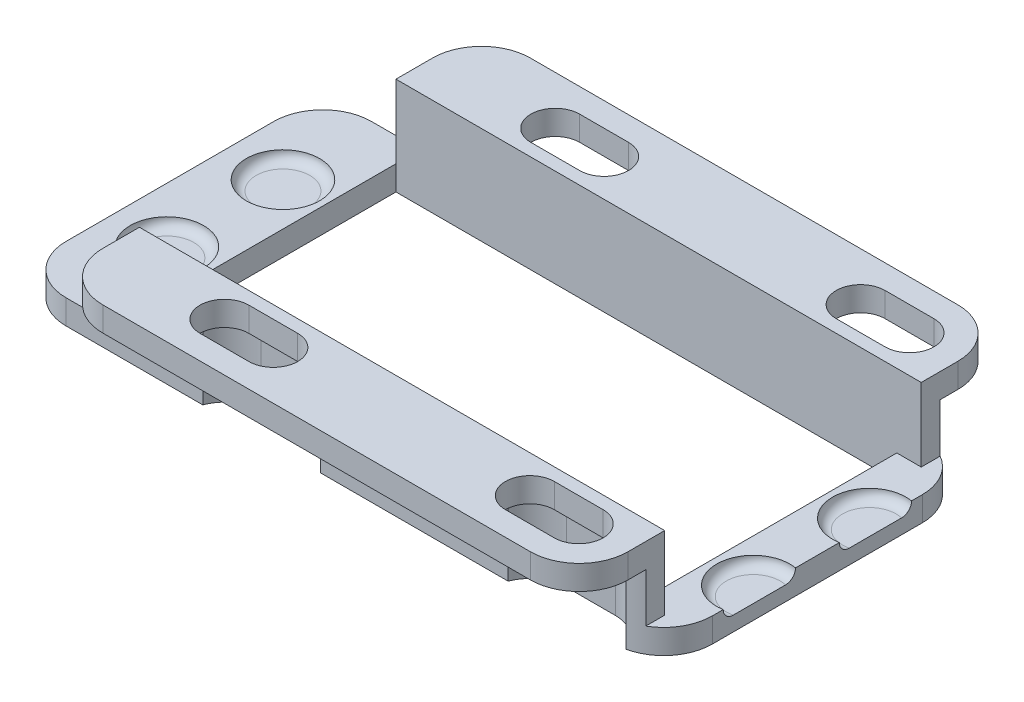
SolidWorks part; units mm, degrees
material "自定义塑料"
ref_plane "前视基准面" through (0, 0, 0) normal (0, 0, 1) x (1, 0, 0)
ref_plane "上视基准面" through (0, 0, 0) normal (0, 1, 0) x (1, 0, 0)
ref_plane "右视基准面" through (0, 0, 0) normal (1, 0, 0) x (0, 0, -1)
sketch "草图4" plane through (0, 0, 0) normal (0, 1, 0) x (1, 0, 0)
  line L0 (20.5, 10.5) -> (24.5, 10.5)
  line L1 (-20.5, 10.5) -> (20.5, 10.5)
  line L2 (-20.5, 10.5) -> (-20.5, -10.5)
  line L3 (-20.5, -10.5) -> (20.5, -10.5)
  line L4 (20.5, 10.5) -> (20.5, -10.5)
  line L5 (-20.5, 10.5) -> (20.5, -10.5) construction
  line L6 (-20.5, -10.5) -> (20.5, 10.5) construction
  line L7 (24.5, 10.5) -> (24.5, 12.5)
  line L9 (-24.5, -12.5) -> (24.5, -12.5)
  line L11 (-24.5, 12.5) -> (24.5, 12.5)
  line L12 (24.5, -12.5) -> (24.5, 12.5)
  line L13 (-24.5, -12.5) -> (24.5, 12.5) construction
  line L14 (-24.5, 12.5) -> (24.5, -12.5) construction
  line L15 (-24.5, 12.5) -> (-28.5, 12.5)
  line L17 (-24.5, -12.5) -> (-28.5, -12.5)
  line L18 (-28.5, 12.5) -> (-28.5, -12.5)
  point P0 (0, 0)
  point P5 (0, 0)
extrude "凸台-拉伸2" add sketch "草图4" along normal blind 2 contours L15 L18 L17 L9 L12 L4 L3 L2 L1 L7 L11 region at (23.914, 0, 1)
sketch "草图5" plane through (0, 2, 0) normal (0, 1, 0) x (1, 0, 0)
  line L1 (-24, 4.75) -> (24, 4.75)
  line L2 (-24, 4.75) -> (-24, -4.75)
  line L3 (-24, -4.75) -> (24, -4.75)
  line L4 (24, 4.75) -> (24, -4.75)
  line L5 (-24, 4.75) -> (24, -4.75) construction
  line L6 (-24, -4.75) -> (24, 4.75) construction
  circle A0 centre (-24, 4.75) radius 3
  circle A1 centre (-24, -4.75) radius 3
  circle A2 centre (24, 4.75) radius 3
  circle A3 centre (24, -4.75) radius 3
  point P0 (0, 0)
  line M3 (24.5, -12.5) -> (24.5, 12.5)
  dimension "D1" = 48
  dimension "D2" = 9.5
extrude "切除-拉伸2" cut sketch "草图5" against normal blind 0.8 contours L1 A0 L2 | L2 A0 L1 | L2 A1 L3 | L3 A1 L2 | L1 A2 L4 | L4 A2 L1 M3 | A3 L4 L3 M3 | L4 A3 L3 region at (-24.4244, 2, -5.1744) region at (-22.7268, 2, -3.4768) region at (23.179, 2, -5.6451) region at (22.7268, 2, -3.4768) region at (-22.7268, 2, 3.4768) region at (-24.4244, 2, 5.1744) region at (23.179, 2, 5.6451) region at (22.7268, 2, 3.4768)
fillet "圆角1" radius 0.8 4 edges at (21, 1.2, 4.75) (21, 1.2, -4.75) (-24, 1.2, 7.75) (-24, 1.2, -1.75)
sketch "草图6" plane through (0, 2, 0) normal (0, 1, 0) x (1, 0, 0)
  line L0 (24.5, 12.5) -> (-28.5, 12.5) construction
  line L1 (-20.5, 10.5) -> (22.5, 10.5)
  line L2 (-20.5, 10.5) -> (-20.5, 12.5)
  line L3 (-20.5, 12.5) -> (22.5, 12.5)
  line L4 (22.5, 10.5) -> (22.5, 12.5)
  line L5 (24.5, -12.5) -> (-28.5, -12.5) construction
  line L6 (-20.5, -10.5) -> (22.5, -10.5)
  line L7 (-20.5, -10.5) -> (-20.5, -12.5)
  line L8 (-20.5, -12.5) -> (22.5, -12.5)
  line L9 (22.5, -10.5) -> (22.5, -12.5)
extrude "凸台-拉伸3" add sketch "草图6" along normal blind 4
sketch "草图7" plane through (0, 6, 0) normal (0, 1, 0) x (1, 0, 0)
  line L1 (-20.5, 10.5) -> (22.5, 10.5)
  line L2 (-20.5, 10.5) -> (-20.5, 17.5)
  line L3 (-20.5, 17.5) -> (22.5, 17.5)
  line L4 (22.5, 10.5) -> (22.5, 17.5)
  line L5 (-20.5, -10.5) -> (22.5, -10.5)
  line L6 (-20.5, -10.5) -> (-20.5, -17.5)
  line L7 (-20.5, -17.5) -> (22.5, -17.5)
  line L8 (22.5, -10.5) -> (22.5, -17.5)
  dimension "D1" = 7
  dimension "D2" = 7
extrude "凸台-拉伸4" add sketch "草图7" along normal blind 2
sketch "草图8" plane through (0, 0, 0) normal (0, -1, 0) x (1, 0, 0)
  line L0 (-10.5, -15.54) -> (-6.5, -15.54)
  line L1 (-4.5, -13.54) -> (16.5, -13.54)
  line L2 (-8.5, -11.54) -> (-8.5, 13.54)
  line L3 (-8.5, 13.54) -> (16.5, 13.54)
  line L4 (16.5, -13.54) -> (16.5, 13.54)
  line L5 (-8.5, -13.54) -> (16.5, 13.54) construction
  line L6 (-8.5, 13.54) -> (16.5, -13.54) construction
  line L7 (-10.5, -11.54) -> (-6.5, -11.54)
  line L8 (14.5, -15.54) -> (18.5, -15.54)
  line L9 (14.5, -11.54) -> (18.5, -11.54)
  line L10 (14.5, 11.54) -> (18.5, 11.54)
  line L11 (14.5, 15.54) -> (18.5, 15.54)
  line L12 (-10.5, 11.54) -> (-6.5, 11.54)
  line L13 (-10.5, 15.54) -> (-6.5, 15.54)
  line L14 (-10.5, -15.54) -> (14.5, -15.54) construction
  arc A1 (-10.5, -11.54) -> (-10.5, -15.54) centre (-10.5, -13.54) ccw
  arc A2 (-6.5, -15.54) -> (-6.6595, -11.5464) centre (-6.5, -13.54) ccw
  arc A3 (14.5, -11.54) -> (14.5, -15.54) centre (14.5, -13.54) ccw
  arc A4 (18.5, -15.54) -> (18.3405, -11.5464) centre (18.5, -13.54) ccw
  arc A5 (14.5, 15.54) -> (14.5, 11.54) centre (14.5, 13.54) ccw
  arc A6 (18.5, 11.54) -> (18.3405, 15.5336) centre (18.5, 13.54) ccw
  arc A7 (-10.5, 15.54) -> (-10.5, 11.54) centre (-10.5, 13.54) ccw
  arc A8 (-6.5, 11.54) -> (-6.6595, 15.5336) centre (-6.5, 13.54) ccw
  point P0 (0, 0)
  point P1 (4, 0)
  point P3 (4, 0)
  point P12 (0, 0)
  line M29 (24.5, 12.5) -> (-28.5, 12.5)
  line M31 (-28.5, -12.5) -> (24.5, -12.5)
  dimension "D2" = 2
  dimension "D1" = 4
  dimension "D3" = 2
  dimension "D4" = 25
extrude "切除-拉伸3" cut sketch "草图8" against normal through all contours L0 A2 A1 M31 | A2 L7 A1 M31 | L12 A8 L2 M29 | A7 L12 L2 M29 | L3 A8 L13 A7 L2 M29 | A8 L3 L2 M29 | L9 A3 L4 M31 | L8 A4 L4 L1 A3 M31 | A3 L1 L4 M31 | A4 L9 L4 M31 | A6 L11 A5 L3 L4 M29 | L10 A6 L4 M29 | A5 L10 L4 M29 | L3 A5 L4 M29 | L11 A5 L10 A6 region at (-8.5, 0, -13.9488) region at (-8.5, 0, -12.0527) region at (14.5462, 0, -13.0264) region at (16.9326, 0, -14.1531) region at (14.8721, 0, -12.0527) region at (-10.1279, 0, 12.0527) region at (-6.8721, 0, 12.0527) region at (18.1279, 0, -12.0527) region at (-8.9326, 0, 14.1531) region at (-6.5462, 0, 13.0264) region at (14.8721, 0, 12.0527) region at (18.1279, 0, 12.0527) region at (14.5462, 0, 13.0264) region at (16.9326, 0, 14.1531)
sketch "草图9" plane through (0, 0, 0) normal (0, -1, 0) x (1, 0, 0)
  line L0 (14.5, -10.54) -> (18.5, -10.54)
  line L1 (18.5, -13.54) -> (-10.5, -13.54)
  line L2 (18.5, -10.54) -> (18.5, 13.54)
  line L3 (18.5, 13.54) -> (-10.5, 13.54)
  line L4 (-10.5, -13.54) -> (-10.5, 13.54)
  line L5 (-10.5, -10.54) -> (-6.5, -10.54)
  line L6 (18.5, -16.54) -> (14.5, -16.54)
  line L7 (-6.5, -16.54) -> (-10.5, -16.54)
  line L8 (-10.5, 16.54) -> (-6.5, 16.54)
  line L9 (-6.5, 10.54) -> (-10.5, 10.54)
  line L10 (14.5, 16.54) -> (18.5, 16.54)
  line L11 (18.5, 10.54) -> (14.5, 10.54)
  line L12 (14.5, -10.54) -> (-10.5, -10.54) construction
  arc A0 (18.5, -16.54) -> (18.5, -10.54) centre (18.5, -13.54) ccw
  arc A2 (14.5, -10.54) -> (14.5, -16.54) centre (14.5, -13.54) ccw
  arc A3 (-6.5, -16.54) -> (-6.5, -10.54) centre (-6.5, -13.54) ccw
  arc A4 (-10.5, -10.54) -> (-10.5, -16.54) centre (-10.5, -13.54) ccw
  arc A5 (-6.5, 10.54) -> (-6.5, 16.54) centre (-6.5, 13.54) ccw
  arc A6 (-10.5, 16.54) -> (-10.5, 10.54) centre (-10.5, 13.54) ccw
  arc A7 (18.5, 10.54) -> (18.5, 16.54) centre (18.5, 13.54) ccw
  arc A8 (14.5, 16.54) -> (14.5, 10.54) centre (14.5, 13.54) ccw
  dimension "D1" = 6
  dimension "D2" = 2
  dimension "D4" = 25
  dimension "D3" = 2
extrude "切除-拉伸5" cut sketch "草图9" against normal blind 6 contours A8 L11 A7 L10 | A5 L8 A6 L9 | L0 A2 L6 A0 | A3 L5 A4 L7
fillet "圆角2" radius 4 4 edges at (24.5, 1, 12.5) (24.5, 1, -12.5) (22.5, 7, -17.5) (22.5, 7, 17.5)
fillet "圆角3" radius 4 2 edges at (-28.5, 1, 12.5) (-28.5, 1, -12.5)
fillet "圆角4" radius 4 2 edges at (-20.5, 7, -17.5) (-20.5, 7, 17.5)
